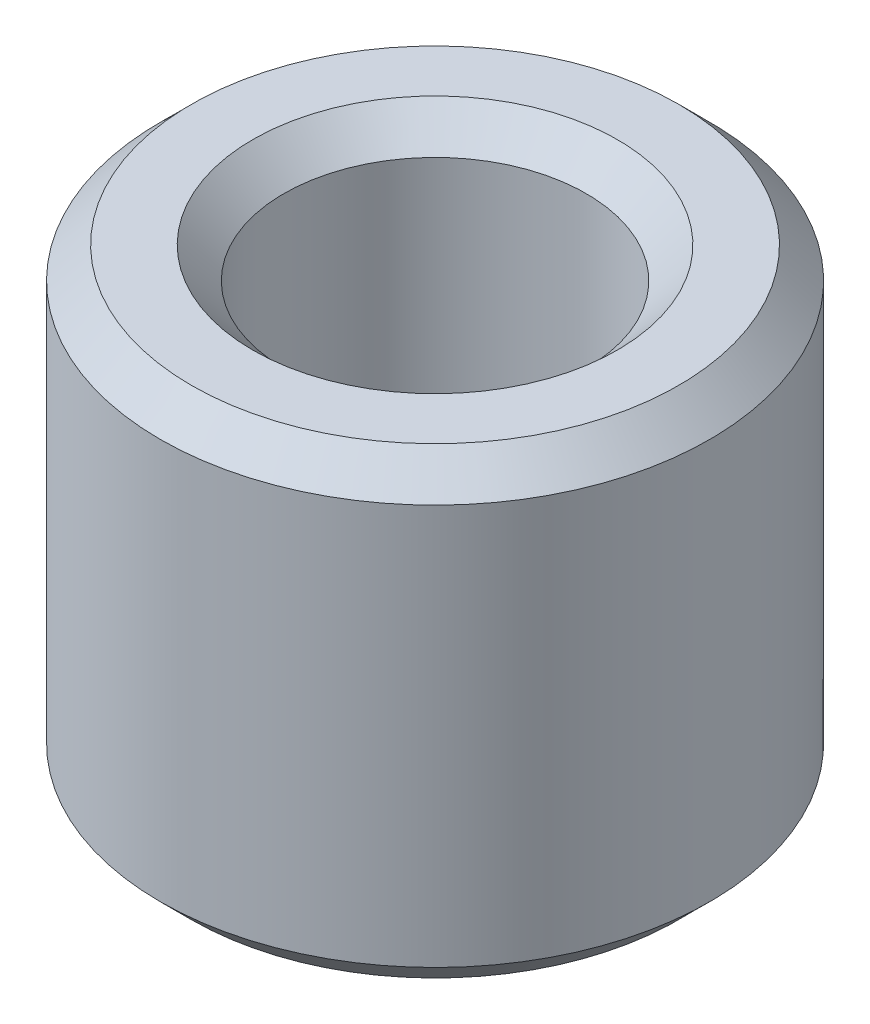
SolidWorks part; units mm, degrees
ref_plane "Front Plane" through (0, 0, 0) normal (0, 0, 1) x (1, 0, 0)
ref_plane "Top Plane" through (0, 0, 0) normal (0, 1, 0) x (1, 0, 0)
ref_plane "Right Plane" through (0, 0, 0) normal (1, 0, 0) x (0, 0, -1)
sketch "Sketch1" plane through (0, 0, 0) normal (0, 1, 0) x (1, 0, 0)
  circle A0 centre (0, 0) radius 22.5
  dimension "SLEEVE_OD" = 45
extrude "Boss-Extrude1" add sketch "Sketch1" along normal blind 37.8963
sketch "Sketch2" plane through (0, 0, 0) normal (0, 1, 0) x (1, 0, 0)
  circle A0 centre (0, 0) radius 12.38
  dimension "BORE_D" = 24.7601
extrude "Cut-Extrude1" cut sketch "Sketch2" along normal through all
chamfer "Chamfer1" distance 2.5529 angle 45 4 edges at (0, 37.8963, 12.38) (0, 0, 12.38) (0, 0, 22.5) (0, 37.8963, 22.5)
